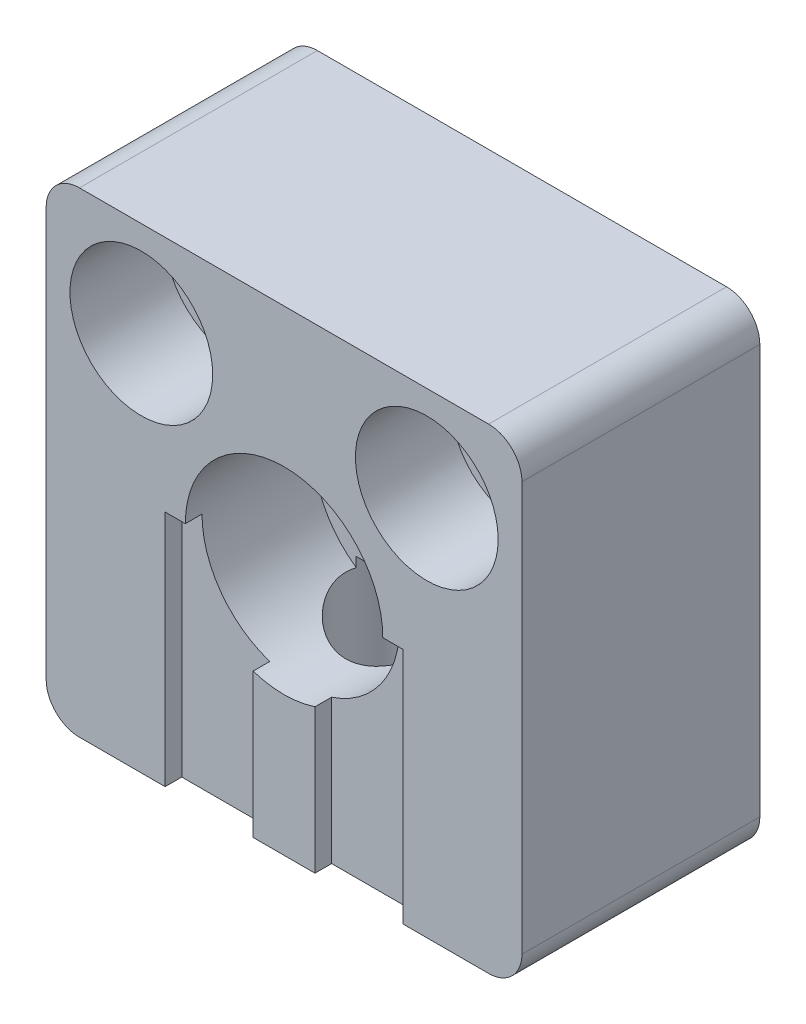
SolidWorks part; units mm, degrees
ref_plane "Front Plane" through (0, 0, 0) normal (0, 0, 1) x (1, 0, 0)
ref_plane "Top Plane" through (0, 0, 0) normal (0, 1, 0) x (1, 0, 0)
ref_plane "Right Plane" through (0, 0, 0) normal (1, 0, 0) x (0, 0, -1)
sketch "Sketch1" plane through (0, 0, 0) normal (0, 1, 0) x (1, 0, 0)
  line L1 (0, 0) -> (10, 0)
  line L2 (0, 0) -> (0, 5)
  line L3 (0, 5) -> (10, 5)
  line L4 (10, 0) -> (10, 5)
  dimension "D1" = 5
  dimension "D2" = 10
extrude "Boss-Extrude1" add sketch "Sketch1" along normal blind 10
sketch "Sketch2" plane through (0, 0, 0) normal (0, 0, 1) x (1, 0, 0)
  line L0 (5, 10) -> (5, 0) construction
  line L1 (0, 10) -> (10, 10) construction
  line L2 (0, 0) -> (10, 0) construction
  line L3 (0, 5) -> (10, 5) construction
  line L4 (0, 10) -> (0, 0) construction
  line L5 (10, 10) -> (10, 0) construction
  circle A0 centre (5, 5) radius 1.575
  dimension "D1" = 3.15
extrude "Cut-Extrude1" cut sketch "Sketch2" against normal through all
sketch "Sketch3" plane through (0, 0, 0) normal (0, 0, 1) x (1, 0, 0)
  line L0 (0, 5) -> (10, 5) construction
  line L1 (0, 10) -> (0, 0) construction
  line L2 (10, 10) -> (10, 0) construction
  line L3 (5, 10) -> (5, 0) construction
  line L4 (0, 10) -> (10, 10) construction
  line L5 (0, 0) -> (10, 0) construction
  circle A0 centre (5, 5) radius 2.075
  dimension "D1" = 4.15
extrude "Cut-Extrude2" cut sketch "Sketch3" against normal blind 2.7
sketch "Sketch5" plane through (0, 0, 0) normal (0, -1, 0) x (1, 0, 0)
  line L0 (0, 0) -> (10, 0) construction
  line L1 (2.5, 0) -> (4.35, 0)
  line L2 (2.5, 0) -> (2.5, -0.35)
  line L3 (2.5, -0.35) -> (4.35, -0.35)
  line L4 (4.35, 0) -> (4.35, -0.35)
  line L5 (0, -5) -> (0, 0) construction
  line L6 (5.65, 0) -> (7.5, 0)
  line L7 (5.65, 0) -> (5.65, -0.35)
  line L8 (5.65, -0.35) -> (7.5, -0.35)
  line L9 (7.5, 0) -> (7.5, -0.35)
  line L10 (10, 0) -> (10, -5) construction
  dimension "D1" = 2.5
  dimension "D2" = 2.5
  dimension "D3" = 1.3
  dimension "D4" = 1.85
  dimension "D5" = 0.35
  dimension "D6" = 0.35
extrude "Cut-Extrude3" cut sketch "Sketch5" against normal blind 5
sketch "Sketch6" plane through (0, 0, 0) normal (0, 0, 1) x (1, 0, 0)
  line L0 (0, 10) -> (10, 10) construction
  line L1 (0, 10) -> (0, 0) construction
  line L2 (10, 10) -> (10, 0) construction
  circle A0 centre (2, 8) radius 1.5
  circle A1 centre (8, 8) radius 1.5
  dimension "D1" = 3
  dimension "D4" = 3
  dimension "D2" = 2
  dimension "D3" = 2
  dimension "D5" = 2
  dimension "D6" = 2
extrude "Cut-Extrude4" cut sketch "Sketch6" against normal blind 2
sketch "Sketch8" plane through (0, 0, 0) normal (0, -1, 0) x (1, 0, 0)
  line L0 (0, -2.5) -> (10, -2.5) construction
  line L1 (0, -5) -> (0, 0) construction
  line L2 (10, 0) -> (10, -5) construction
  circle A0 centre (5, -2.5) radius 1.2
  dimension "D1" = 2.4
extrude "Cut-Extrude5" cut sketch "Sketch8" against normal blind 3.5
fillet "Fillet1" radius 0.7 4 edges at (0, 10, -2.5) (0, 0, -2.5) (10, 0, -2.5) (10, 10, -2.5)
